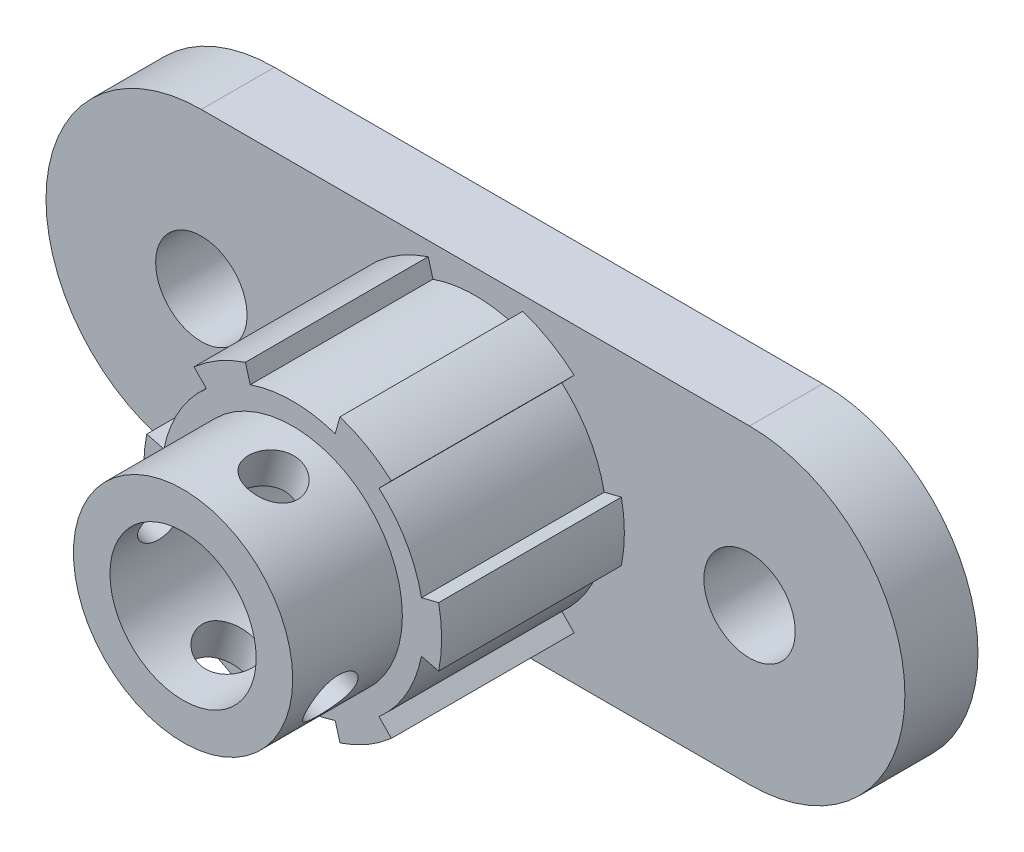
SolidWorks part; units mm, degrees
ref_plane "Front Plane" through (0, 0, 0) normal (0, 0, 1) x (1, 0, 0)
ref_plane "Top Plane" through (0, 0, 0) normal (0, 1, 0) x (1, 0, 0)
ref_plane "Right Plane" through (0, 0, 0) normal (1, 0, 0) x (0, 0, -1)
sketch "Sketch1" plane through (0, 0, 0) normal (0, 0, 1) x (1, 0, 0)
  point P0 (0, 0)
  line B0 (-2.05, 7.2975) -> (-2.3123, 8.2314)
  line B1 (-5.9724, 6.1182) -> (-5.2948, 5.4241)
  line B2 (-7.3448, 1.8734) -> (-8.2848, 2.1131)
  line B3 (-8.2848, -2.1131) -> (-7.3448, -1.8734)
  line B4 (-5.2948, -5.4241) -> (-5.9724, -6.1182)
  line B5 (-2.3123, -8.2314) -> (-2.05, -7.2975)
  line B6 (2.05, -7.2975) -> (2.3123, -8.2314)
  line B7 (5.9724, -6.1182) -> (5.2948, -5.4241)
  line B8 (7.3448, -1.8734) -> (8.2848, -2.1131)
  line B9 (8.2848, 2.1131) -> (7.3448, 1.8734)
  line B10 (5.2948, 5.4241) -> (5.9724, 6.1182)
  line B11 (2.3123, 8.2314) -> (2.05, 7.2975)
  arc B12 (2.05, 7.2975) -> (-2.05, 7.2975) centre (0, 0) ccw
  arc B13 (-2.3123, 8.2314) -> (-5.9724, 6.1182) centre (0, 0) ccw
  arc B14 (-5.2948, 5.4241) -> (-7.3448, 1.8734) centre (0, 0) ccw
  arc B15 (-8.2848, 2.1131) -> (-8.2848, -2.1131) centre (0, 0) ccw
  arc B16 (-7.3448, -1.8734) -> (-5.2948, -5.4241) centre (0, 0) ccw
  arc B17 (-5.9724, -6.1182) -> (-2.3123, -8.2314) centre (0, 0) ccw
  arc B18 (-2.05, -7.2975) -> (2.05, -7.2975) centre (0, 0) ccw
  arc B19 (2.3123, -8.2314) -> (5.9724, -6.1182) centre (0, 0) ccw
  arc B20 (5.2948, -5.4241) -> (7.3448, -1.8734) centre (0, 0) ccw
  arc B21 (8.2848, -2.1131) -> (8.2848, 2.1131) centre (0, 0) ccw
  arc B22 (7.3448, 1.8734) -> (5.2948, 5.4241) centre (0, 0) ccw
  arc B23 (5.9724, 6.1182) -> (2.3123, 8.2314) centre (0, 0) ccw
  circle B24 centre (-15, 0) radius 2.5
  circle B25 centre (15, 0) radius 2.5
sketch_block_instance "Block2-1"
sketch_block "Block2"
sketch "Sketch3" plane through (0, 0, 0) normal (0, 0, 1) x (1, 0, 0)
  line L24 (-7.9865, -1.6243) -> (-7.0453, -1.3842)
  line L25 (-7.0453, 1.3842) -> (-7.9865, 1.6243)
  line L26 (-4.7214, -5.4093) -> (-5.3999, -6.1044)
  line L27 (2.3239, -6.7935) -> (2.5866, -7.7287)
  line L28 (-2.5866, -7.7287) -> (-2.3239, -6.7935)
  line L29 (5.3999, -6.1044) -> (4.7214, -5.4093)
  line L30 (7.0453, -1.3842) -> (7.9865, -1.6243)
  line L31 (7.9865, 1.6243) -> (7.0453, 1.3842)
  line L32 (4.7214, 5.4093) -> (5.3999, 6.1044)
  line L33 (2.5866, 7.7287) -> (2.3239, 6.7935)
  line L34 (-2.3239, 6.7935) -> (-2.5866, 7.7287)
  line L35 (-5.3999, 6.1044) -> (-4.7214, 5.4093)
  line L36 (-7.9865, -1.6243) -> (-7.0453, -1.3842)
  line L37 (-7.0453, 1.3842) -> (-7.9865, 1.6243)
  line L38 (-4.7214, -5.4093) -> (-5.3999, -6.1044)
  line L39 (2.3239, -6.7935) -> (2.5866, -7.7287)
  line L40 (-2.5866, -7.7287) -> (-2.3239, -6.7935)
  line L41 (5.3999, -6.1044) -> (4.7214, -5.4093)
  line L42 (7.0453, -1.3842) -> (7.9865, -1.6243)
  line L43 (7.9865, 1.6243) -> (7.0453, 1.3842)
  line L44 (4.7214, 5.4093) -> (5.3999, 6.1044)
  line L45 (2.5866, 7.7287) -> (2.3239, 6.7935)
  line L46 (-2.3239, 6.7935) -> (-2.5866, 7.7287)
  line L47 (-5.3999, 6.1044) -> (-4.7214, 5.4093)
  arc A25 (-7.9865, 1.6243) -> (-7.9865, -1.6243) centre (0, 0) ccw
  arc A26 (-7.0453, -1.3842) -> (-4.7214, -5.4093) centre (0, 0) ccw
  arc A27 (-5.3999, -6.1044) -> (-2.5866, -7.7287) centre (0, 0) ccw
  arc A28 (-2.3239, -6.7935) -> (2.3239, -6.7935) centre (0, 0) ccw
  arc A29 (2.5866, -7.7287) -> (5.3999, -6.1044) centre (0, 0) ccw
  arc A30 (4.7214, -5.4093) -> (7.0453, -1.3842) centre (0, 0) ccw
  arc A31 (7.9865, -1.6243) -> (7.9865, 1.6243) centre (0, 0) ccw
  arc A32 (7.0453, 1.3842) -> (4.7214, 5.4093) centre (0, 0) ccw
  arc A33 (5.3999, 6.1044) -> (2.5866, 7.7287) centre (0, 0) ccw
  arc A34 (2.3239, 6.7935) -> (-2.3239, 6.7935) centre (0, 0) ccw
  arc A35 (-2.5866, 7.7287) -> (-5.3999, 6.1044) centre (0, 0) ccw
  arc A36 (-4.7214, 5.4093) -> (-7.0453, 1.3842) centre (0, 0) ccw
  arc A37 (-7.9865, 1.6243) -> (-7.9865, -1.6243) centre (0, 0) ccw
  arc A38 (-7.0453, -1.3842) -> (-4.7214, -5.4093) centre (0, 0) ccw
  arc A39 (-5.3999, -6.1044) -> (-2.5866, -7.7287) centre (0, 0) ccw
  arc A40 (-2.3239, -6.7935) -> (2.3239, -6.7935) centre (0, 0) ccw
  arc A41 (2.5866, -7.7287) -> (5.3999, -6.1044) centre (0, 0) ccw
  arc A42 (4.7214, -5.4093) -> (7.0453, -1.3842) centre (0, 0) ccw
  arc A43 (7.9865, -1.6243) -> (7.9865, 1.6243) centre (0, 0) ccw
  arc A44 (7.0453, 1.3842) -> (4.7214, 5.4093) centre (0, 0) ccw
  arc A45 (5.3999, 6.1044) -> (2.5866, 7.7287) centre (0, 0) ccw
  arc A46 (2.3239, 6.7935) -> (-2.3239, 6.7935) centre (0, 0) ccw
  arc A47 (-2.5866, 7.7287) -> (-5.3999, 6.1044) centre (0, 0) ccw
  arc A48 (-4.7214, 5.4093) -> (-7.0453, 1.3842) centre (0, 0) ccw
  dimension "D1" = 0.4
extrude "Boss-Extrude1" add sketch "Sketch3" along normal blind 10
sketch "Sketch4" plane through (0, 0, 0) normal (0, 0, -1) x (-1, 0, 0)
  line L0 (-15, 0) -> (15, 0) construction
  line L1 (-15, 8.5) -> (15, 8.5)
  line L2 (-15, -8.5) -> (15, -8.5)
  arc A0 (-15, 8.5) -> (-15, -8.5) centre (-15, 0) ccw
  arc A1 (15, -8.5) -> (15, 8.5) centre (15, 0) ccw
  circle A2 centre (15, 0) radius 2.5 construction
  circle A3 centre (-15, 0) radius 2.5 construction
  circle A4 centre (15, 0) radius 2.5
  circle A5 centre (-15, 0) radius 2.5
  point P4 (0, 0)
  dimension "D1" = 17
extrude "Boss-Extrude2" add sketch "Sketch4" along normal blind 4
sketch "Sketch5" plane through (0, 0, -4) normal (0, 0, -1) x (-1, 0, 0)
  circle A0 centre (0, 0) radius 4
  dimension "D1" = 8
extrude "Cut-Extrude1" cut sketch "Sketch5" against normal through all
sketch "Sketch6" plane through (0, 0, 10) normal (0, 0, 1) x (1, 0, 0)
  circle A0 centre (0, 0) radius 4 construction
  circle A1 centre (0, 0) radius 4
  circle A2 centre (0, 0) radius 6
  dimension "D1" = 2
extrude "Boss-Extrude3" add sketch "Sketch6" along normal blind 6
hole_wizard "Ø1.0mm Dowel Hole1" positions "3DSketch1" profile "Sketch7" hole size "Ø1.0" standard "ANSI Metric"
sketch3d "3DSketch1"
  point P0 (-1.574, -5.7899, 12.6051)
  point P2 (5.4512, -2.5069, 13.3704)
sketch "Sketch7" plane through (-1.574, -5.7899, 12.6051) normal (0, 0, 1) x (0.965, -0.2623, 0)
  line L0 (0, 0) -> (0, 34)
  line L1 (0, 34) -> (1.4, 33.1588)
  line L2 (1.4, 33.1588) -> (1.4, 0)
  line L5 (1.4, 0) -> (0, 0)
  line L10 (0, 34) -> (-1.4, 33.1588) construction
  line L11 (0, -6.35) -> (0, 107.95) construction
  dimension "Hole Dia." = 2.8
  dimension "Hole Depth" = 34
  dimension "Drill Angle" = 118
